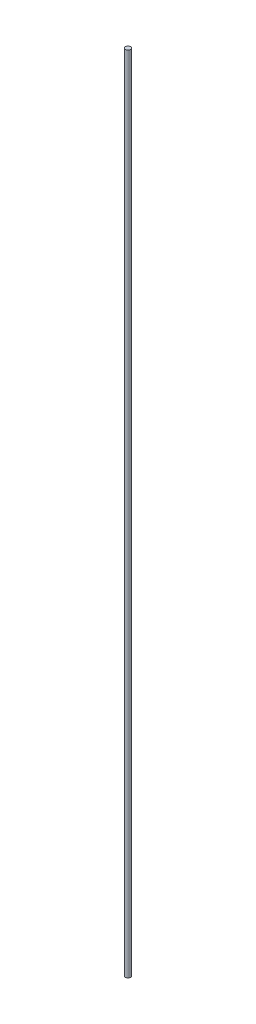
SolidWorks part; units mm, degrees
ref_plane "Front Plane" through (0, 0, 0) normal (0, 0, 1) x (1, 0, 0)
ref_plane "Top Plane" through (0, 0, 0) normal (0, 1, 0) x (1, 0, 0)
ref_plane "Right Plane" through (0, 0, 0) normal (1, 0, 0) x (0, 0, -1)
sketch "Sketch1" plane through (0, 0, 0) normal (0, 0, 1) x (1, 0, 0)
  line L0 (0, 0) -> (0, 1993.646)
  dimension "Length from Tank Model" = 1993.646
sweep "Sweep1" add path "Sketch1" circular profile diameter 12.7 parameters "D3"=12.7
equation "\"rebar diameter\"= .5"
equation "\"D3@Sweep1\"=\"rebar diameter\""
